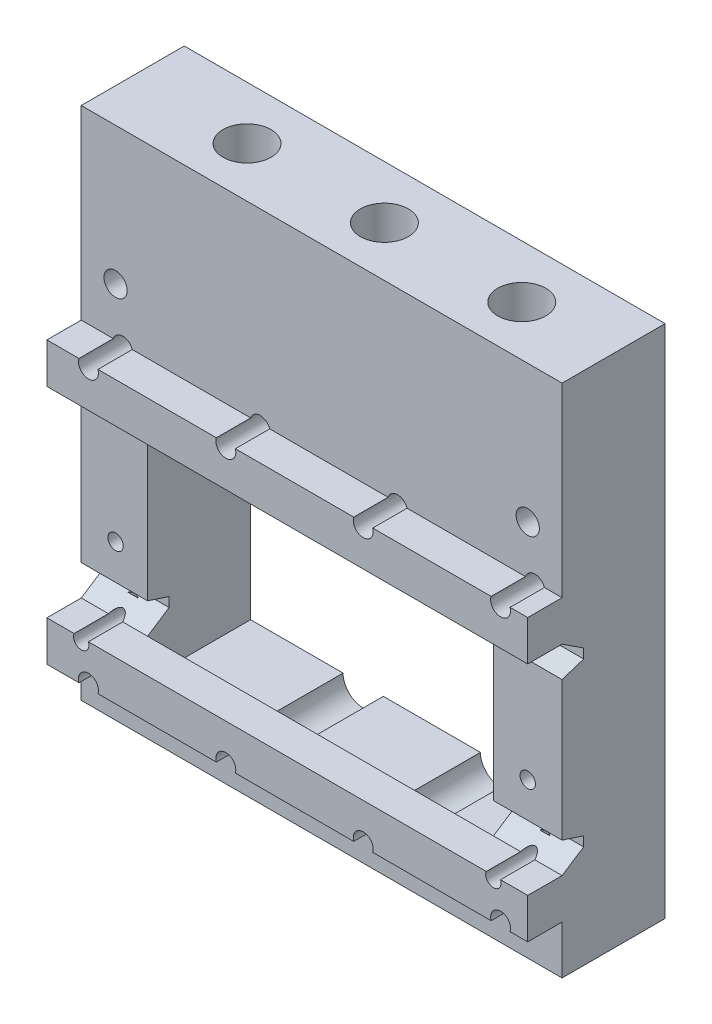
SolidWorks part; units mm, degrees
material "ABS"
ref_plane "Front Plane" through (0, 0, 0) normal (0, 0, 1) x (1, 0, 0)
ref_plane "Top Plane" through (0, 0, 0) normal (0, 1, 0) x (1, 0, 0)
ref_plane "Right Plane" through (0, 0, 0) normal (1, 0, 0) x (0, 0, -1)
sketch "Sketch1" plane through (0, 0, 0) normal (0, 0, 1) x (1, 0, 0)
  line L1 (-63.1034, 106.2931) -> (76.8966, 106.2931)
  line L2 (-63.1034, 106.2931) -> (-63.1034, -43.7069)
  line L3 (-63.1034, -43.7069) -> (76.8966, -43.7069)
  line L4 (76.8966, 106.2931) -> (76.8966, -43.7069)
  line L5 (-43.7931, 31.2931) -> (56.8966, 31.2931)
  line L6 (-43.7931, 31.2931) -> (-43.7931, -28.7069)
  line L7 (-43.7931, -28.7069) -> (56.8966, -28.7069)
  line L8 (56.8966, 31.2931) -> (56.8966, -28.7069)
  dimension "D1" = 60
  dimension "D2" = 150
  dimension "D3" = 75
  dimension "D4" = 140
  dimension "D5" = 20
extrude "Boss-Extrude1" add sketch "Sketch1" along normal blind 30
sketch "Sketch2" plane through (-63.1034, 0, 0) normal (-1, 0, 0) x (0, 0, 1)
  line L0 (30, 40.4671) -> (23.72, 36.3783)
  line L1 (30, 106.2931) -> (30, -43.7069) construction
  line L2 (23.72, 36.3783) -> (23.72, 33.5887)
  line L3 (23.72, 33.5887) -> (30, 31.5444)
  line L4 (30, 31.5444) -> (30, 40.4671)
extrude "Cut-Extrude1" cut sketch "Sketch2" against normal blind 300
ref_plane "Plane1" through (0, 11.2931, 0) normal (0, -1, 0) x (-1, 0, 0)
ref_plane "Plane2" through (0, 46.2931, 0) normal (0, 1, 0) x (1, 0, 0)
sketch "Sketch11" plane through (0, 0, 30) normal (0, 0, 1) x (1, 0, 0)
  line L0 (-63.1034, 106.2931) -> (-63.1034, 40.4671) construction
  line L1 (-63.1034, 52.1826) -> (76.8966, 52.1826)
  line L2 (-63.1034, 52.1826) -> (-63.1034, 40.4671)
  line L3 (-63.1034, 40.4671) -> (76.8966, 40.4671)
  line L4 (76.8966, 52.1826) -> (76.8966, 40.4671)
  line L5 (76.8966, 40.4671) -> (76.8966, 106.2931) construction
extrude "Boss-Extrude2" add sketch "Sketch11" along normal blind 10
mirror "Mirror1" about plane through (0, 11.2931, 0) normal (0, -1, 0) of "Boss-Extrude2", "Cut-Extrude1"
sketch "Sketch3" plane through (0, 106.2931, 0) normal (0, 1, 0) x (1, 0, 0)
  circle A0 centre (-29.4046, -15.4362) radius 3
extrude "Cut-Extrude2" cut sketch "Sketch3" against normal blind 100
sketch "Sketch4" plane through (0, 106.2931, 0) normal (0, 1, 0) x (1, 0, 0)
  circle A0 centre (-29.4046, -15.4362) radius 7
  circle A1 centre (-29.4046, -15.4362) radius 3 construction
extrude "Cut-Extrude3" cut sketch "Sketch4" against normal blind 70
pattern_linear "LPattern1" count 3 spacing 40 along (1, 0, 0) of "Cut-Extrude2", "Cut-Extrude3"
sketch "Sketch5" plane through (0, 0, 0) normal (0, 0, -1) x (-1, 0, 0)
  line L0 (63.1034, 106.2931) -> (63.1034, -43.7069) construction
  line L1 (43.7931, -28.7069) -> (-56.8966, -28.7069) construction
  circle A0 centre (53.1034, -18.7069) radius 2.2387
  dimension "D1" = 10
  dimension "D2" = 10
extrude "Cut-Extrude4" cut sketch "Sketch5" against normal blind 100
sketch "Sketch6" plane through (0, 0, 0) normal (0, 0, -1) x (-1, 0, 0)
  circle A0 centre (53.1034, -18.7069) radius 4.369
extrude "Cut-Extrude5" cut sketch "Sketch6" against normal blind 25
pattern_linear "LPattern2" count 2 spacing 20 along (0, 1, 0) count 2 spacing 120 along (1, 0, 0) of "Cut-Extrude4", "Cut-Extrude5"
sketch "Sketch7" plane through (0, 0, 0) normal (0, 0, -1) x (-1, 0, 0)
  line L0 (-56.8966, 31.2931) -> (43.7931, 31.2931) construction
  circle A0 centre (51.0031, 51.2931) radius 2.9002
  dimension "D1" = 20
extrude "Cut-Extrude6" cut sketch "Sketch7" against normal blind 40
sketch "Sketch8" plane through (0, 0, 0) normal (0, 0, -1) x (-1, 0, 0)
  circle A0 centre (51.0031, 51.2931) radius 5.871
extrude "Cut-Extrude7" cut sketch "Sketch8" against normal blind 25
pattern_linear "LPattern3" count 4 spacing 40 along (1, 0, 0) count 2 spacing 80 along (0, -1, 0) of "Cut-Extrude6", "Cut-Extrude7"
sketch "Sketch9" plane through (0, 0, 0) normal (0, 0, -1) x (-1, 0, 0)
  line L0 (-76.8966, -43.7069) -> (-76.8966, 106.2931) construction
  line L1 (-76.8966, 106.2931) -> (63.1034, 106.2931) construction
  circle A0 centre (-66.8966, 66.2931) radius 3.3818
  dimension "D1" = 10
  dimension "D2" = 40
extrude "Cut-Extrude8" cut sketch "Sketch9" against normal blind 100
sketch "Sketch10" plane through (0, 0, 30) normal (0, 0, 1) x (1, 0, 0)
  circle A0 centre (66.8966, 66.2931) radius 6.9825
  circle A1 centre (66.8966, 66.2931) radius 3.3818 construction
extrude "Cut-Extrude9" cut sketch "Sketch10" against normal blind 20 from offset 10 offset against normal yes
pattern_linear "LPattern4" count 2 spacing 120 along (-1, 0, 0) of "Cut-Extrude9", "Cut-Extrude8"
